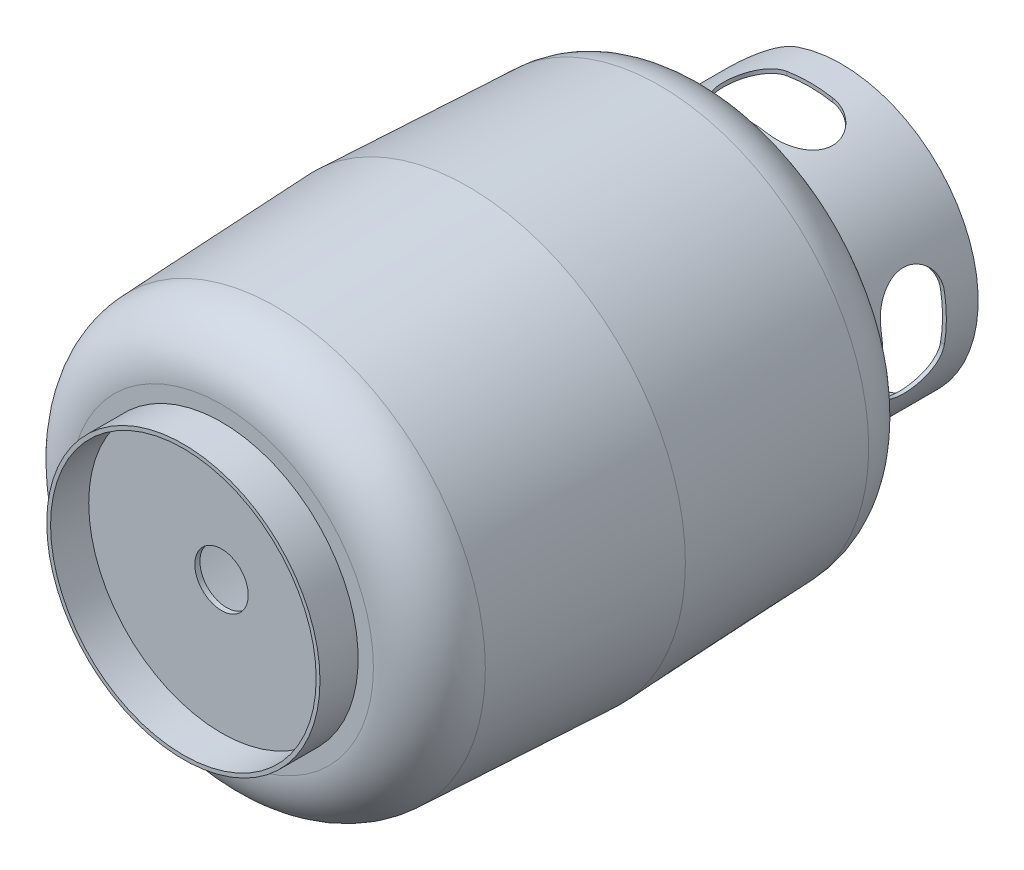
SolidWorks part; units mm, degrees
ref_plane "Front Plane" through (0, 0, 0) normal (0, 0, 1) x (1, 0, 0)
ref_plane "Top Plane" through (0, 0, 0) normal (0, 1, 0) x (1, 0, 0)
ref_plane "Right Plane" through (0, 0, 0) normal (1, 0, 0) x (0, 0, -1)
sketch "Sketch2" plane through (0, 0, 0) normal (0, 1, 0) x (1, 0, 0)
  line L0 (0, 0) -> (0, 387.5) construction
  line L1 (0, 0) -> (-119.4219, 0)
  line L2 (-164.379, 43.0371) -> (-170.9593, 193.75)
  line L3 (-170.9593, 193.75) -> (-164.379, 344.4629)
  line L4 (-119.4219, 387.5) -> (-37, 387.5)
  line L5 (-25, 399.5) -> (-25, 407.5)
  line L6 (-25, 407.5) -> (0, 407.5)
  line L7 (0, 387.5) -> (0, 427.5) construction
  line L8 (0, 4) -> (-119.4219, 4)
  line L9 (-160.3828, 43.2116) -> (-166.9555, 193.75)
  line L10 (-166.9555, 193.75) -> (-160.3828, 344.2884)
  line L11 (-119.4219, 383.5) -> (-37, 383.5)
  line L12 (-21, 399.5) -> (-21, 403.5)
  line L13 (-21, 403.5) -> (0, 403.5)
  line L14 (0, 407.5) -> (0, 403.5)
  line L15 (0, 4) -> (0, 0)
  arc A0 (-119.4219, 0) -> (-164.379, 43.0371) centre (-119.4219, 45) cw
  arc A1 (-164.379, 344.4629) -> (-119.4219, 387.5) centre (-119.4219, 342.5) cw
  arc A2 (-37, 387.5) -> (-25, 399.5) centre (-37, 399.5) ccw
  arc A3 (-119.4219, 4) -> (-160.3828, 43.2116) centre (-119.4219, 45) cw
  arc A4 (-160.3828, 344.2884) -> (-119.4219, 383.5) centre (-119.4219, 342.5) cw
  arc A5 (-37, 383.5) -> (-21, 399.5) centre (-37, 399.5) ccw
  point P13 (-162.5, 0)
  point P16 (-162.5, 387.5)
  point P19 (-25, 387.5)
  dimension "D8" = 45
  dimension "D9" = 45
  dimension "D10" = 12
  dimension "D1" = 387.5
  dimension "D2" = 162.5
  dimension "D3" = 92.5
  dimension "D4" = 92.5
  dimension "D5" = 162.5
  dimension "D6" = 25
  dimension "D7" = 20
  dimension "D11" = 4
revolve "Revolve1" add sketch "Sketch2" angle 360 about L0
sketch "Sketch3" plane through (0, 0, -407.5) normal (0, 0, -1) x (-1, 0, 0)
  circle A0 centre (0, 0) radius 21
  dimension "D1" = 42
extrude "Cut-Extrude1" cut sketch "Sketch3" against normal through all
sketch "Sketch4" plane through (0, 0, -387.5) normal (0, 0, -1) x (-1, 0, 0)
  line L0 (-104.4219, 0) -> (104.4219, 0) construction
  line L1 (0, 0) -> (82.67, 118.0649)
  line L2 (0, 0) -> (84.5106, -120.6936)
  line L3 (61.6147, 87.9948) -> (59.8939, 85.5374)
  line L4 (61.6147, -87.9948) -> (59.8939, -85.5374)
  arc A0 (61.6147, 87.9948) -> (61.6147, -87.9948) centre (0, 0) ccw
  circle A1 centre (0, 0) radius 119.4219 construction
  arc A2 (59.8939, 85.5374) -> (59.8939, -85.5374) centre (0, 0) ccw
  circle A3 centre (0, 0) radius 107.4219 construction
  circle A4 centre (0, 0) radius 104.4219 construction
  point P10 (0, 0)
  dimension "D1" = 12
  dimension "D3" = 55
  dimension "D4" = 55
  dimension "D2" = 3
extrude "Boss-Extrude1" add sketch "Sketch4" along normal blind 100 contours A2 L1 A0 L2 region at (107.1556, 0, -387.5)
sketch "Sketch5" plane through (0, 0, 0) normal (0, 1, 0) x (1, 0, 0)
  line L0 (0, 0) -> (0, 487.5) construction
  line L1 (107.4219, 487.5) -> (-61.6147, 487.5) construction
  line L2 (-18, 437.5) -> (18, 437.5) construction
  line L3 (-18, 462.5) -> (18, 462.5)
  line L4 (-18, 412.5) -> (18, 412.5)
  arc A0 (-18, 462.5) -> (-18, 412.5) centre (-18, 437.5) ccw
  arc A1 (18, 412.5) -> (18, 462.5) centre (18, 437.5) ccw
  point P7 (0, 437.5)
  point P12 (0, 438.564)
  dimension "D2" = 25
  dimension "D1" = 18
  dimension "D3" = 50
extrude "Cut-Extrude2" cut sketch "Sketch5" against normal through all
pattern_circular "CirPattern1" count 3 every 90 about axis through (0, 0, -487.5) along (0, 0, 1) of "Cut-Extrude2"
fillet "Fillet1" radius 30 2 edges at (-60.7543, -86.7661, -487.5) (-60.7543, 86.7661, -487.5)
sketch "Sketch6" plane through (0, 0, 0) normal (0, 0, 1) x (1, 0, 0)
  circle A0 centre (0, 0) radius 107.4219
  circle A1 centre (0, 0) radius 119.4219 construction
  circle A2 centre (0, 0) radius 104.4219
  dimension "D1" = 12
  dimension "D2" = 3
extrude "Boss-Extrude2" add sketch "Sketch6" along normal blind 30
equation "\"a\"= 325"
equation "\"b\"= 387.5"
